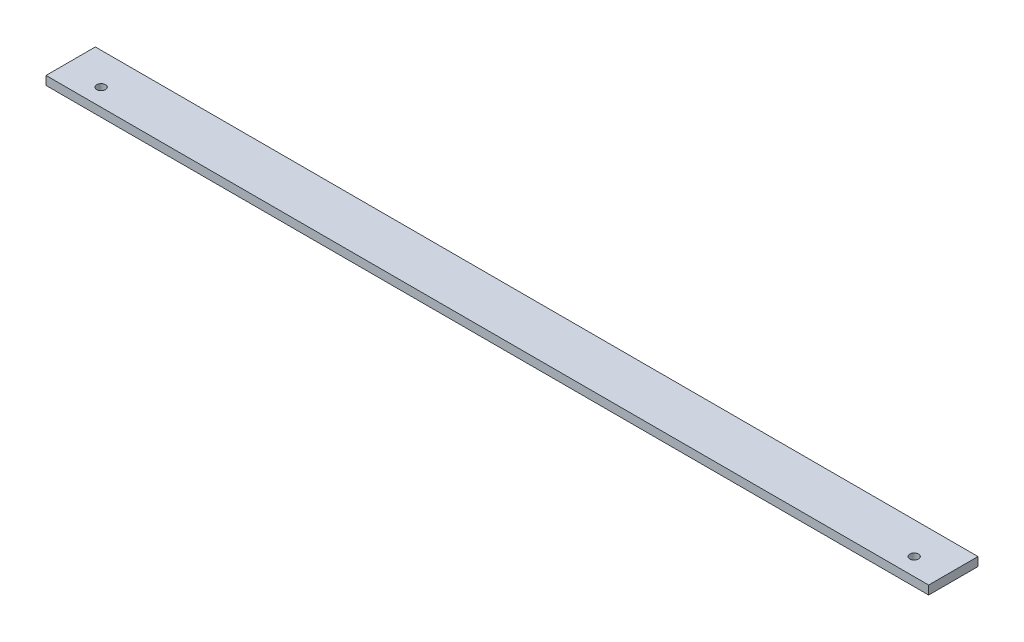
SolidWorks part; units mm, degrees
ref_plane "Front Plane" through (0, 0, 0) normal (0, 0, 1) x (1, 0, 0)
ref_plane "Top Plane" through (0, 0, 0) normal (0, 1, 0) x (1, 0, 0)
ref_plane "Right Plane" through (0, 0, 0) normal (1, 0, 0) x (0, 0, -1)
ref_plane "Plane1" through (0, 3, 0) normal (0, 1, 0) x (1, 0, 0)
sketch "Sketch1" plane through (0, 3, 0) normal (0, 1, 0) x (1, 0, 0)
  line L0 (152, 11) -> (-152, 11)
  line L1 (-152, 11) -> (-152, -6)
  line L2 (-152, -6) -> (152, -6)
  line L3 (152, -6) -> (152, 11)
  circle A0 centre (141, 0) radius 1.5
  circle A1 centre (-139, 0) radius 1.5
extrude "Boss-Extrude1" add sketch "Sketch1" against normal blind 3
